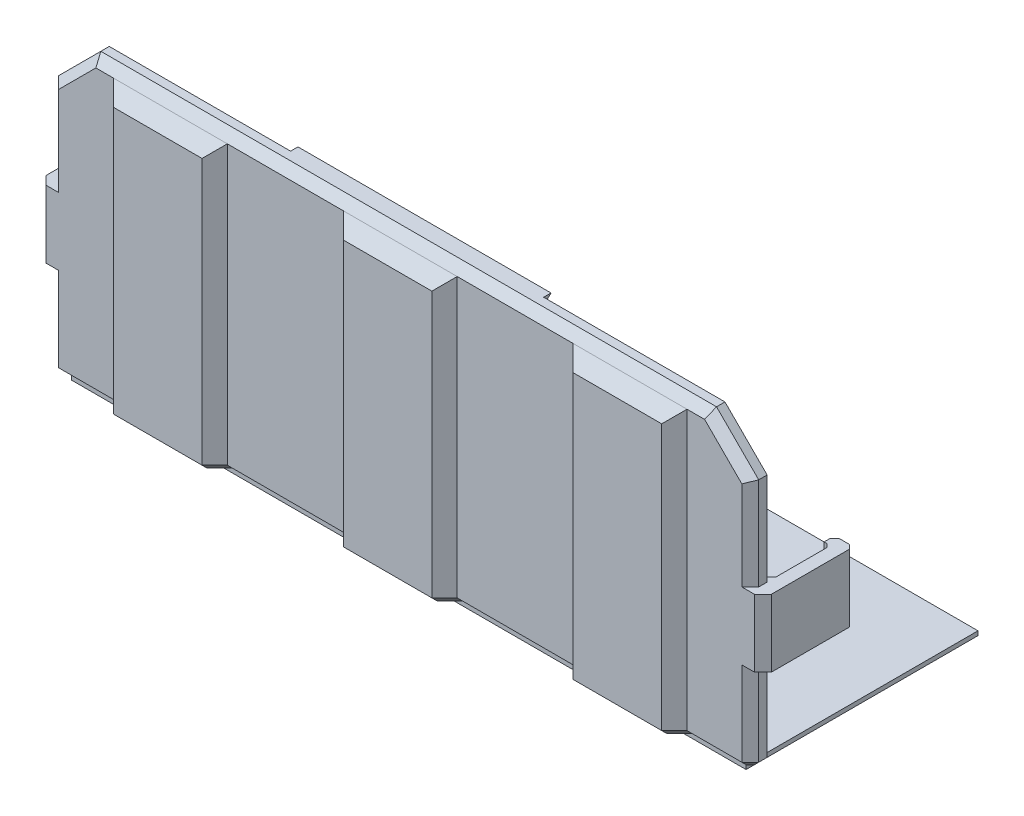
SolidWorks part; units mm, degrees
material "ABS PC"
ref_plane "Front Plane" through (0, 0, 0) normal (0, 0, 1) x (1, 0, 0)
ref_plane "Top Plane" through (0, 0, 0) normal (0, 1, 0) x (1, 0, 0)
ref_plane "Right Plane" through (0, 0, 0) normal (1, 0, 0) x (0, 0, -1)
sketch "Sketch1" plane through (0, 0, 0) normal (0, 0, 1) x (1, 0, 0)
  line L1 (83, -70) -> (-83, -70)
  line L2 (83, -70) -> (83, 0)
  line L3 (83, 0) -> (-83, 0)
  line L4 (-83, -70) -> (-83, 0)
  dimension "D1" = 166
  dimension "D2" = 70
extrude "Boss-Extrude1" add sketch "Sketch1" along normal blind 4
chamfer "Chamfer1" distance 10 angle 45 2 edges at (83, 0, 2) (-83, 0, 2)
chamfer "Chamfer2" distance 2 angle 45 5 edges at (83, -40, 4) (78, -5, 4) (-83, -40, 4) (-78, -5, 4) (0, 0, 4)
sketch "Sketch2" plane through (0, -70, 0) normal (0, -1, 0) x (-1, 0, 0)
  line L0 (68, -4) -> (65, -7)
  line L1 (81, -4) -> (-81, -4) construction
  line L2 (65, -7) -> (44, -7)
  line L3 (44, -7) -> (41, -4)
  line L4 (68, -4) -> (41, -4)
  line L5 (13.5, -4) -> (-13.5, -4)
  line L6 (-13.5, -4) -> (-10.5, -7)
  line L7 (-10.5, -7) -> (10.5, -7)
  line L8 (10.5, -7) -> (13.5, -4)
  line L9 (-41, -4) -> (-44, -7)
  line L10 (-44, -7) -> (-65, -7)
  line L11 (-65, -7) -> (-68, -4)
  line L12 (-68, -4) -> (-41, -4)
  line L13 (-47, 172) -> (-68, 172) construction
  line L14 (11, 172) -> (-11, 172) construction
  point P17 (0, 172)
  point P18 (0, -7)
  dimension "D1" = 45
  dimension "D2" = 3
extrude "Boss-Extrude2" add sketch "Sketch2" against normal up to vertex (68 mm away) up to point (72.1716, -2, 4)
chamfer "Chamfer3" distance 3 angle 45 3 edges at (54.5, -2, 7) (0, -2, 7) (-54.5, -2, 7)
sketch "Sketch3" plane through (0, -70, 0) normal (0, -1, 0) x (-1, 0, 0)
  line L0 (-73, -2) -> (-83, -2) construction
  line L1 (-80, -2) -> (80, -2)
  line L2 (-80, -2) -> (-80, 53)
  line L3 (-80, 53) -> (80, 53)
  line L4 (80, -2) -> (80, 53)
  line L5 (83, -2) -> (73, -2) construction
  dimension "D1" = 55
extrude "Boss-Extrude3" add sketch "Sketch3" along normal blind 3
chamfer "Chamfer4" distance 2 angle 45 3 edges at (0, -73, 2) (-80, -73, -25.5) (80, -73, -25.5)
ref_plane "Plane1" through (-70, 0, 0) normal (-1, 0, 0) x (0, 0, 1)
sketch "Sketch4" plane through (-70, 0, 0) normal (-1, 0, 0) x (0, 0, 1)
  line L0 (0, -70) -> (0, -65)
  line L1 (0, -10) -> (0, -70) construction
  line L2 (0, -65) -> (-5, -70)
  line L3 (0, -70) -> (-53, -70) construction
  line L4 (-5, -70) -> (0, -70)
  dimension "D1" = 5
extrude "Boss-Extrude4" add sketch "Sketch4" against normal offset from surface (140 mm away) 10 up to face at (80, -70.4, -20.4)
ref_plane "Plane2" through (0, -48, 0) normal (0, -1, 0) x (-1, 0, 0)
sketch "Sketch5" plane through (0, -48, 0) normal (0, -1, 0) x (-1, 0, 0)
  line L0 (-81, -4) -> (-83, -2)
  line L1 (-83, -2) -> (-83, 15)
  line L2 (-83, 15) -> (-81.5, 15)
  line L4 (-81.5, 15) -> (-81.5, 16.5)
  line L5 (-82.5, 17.5) -> (-85, 17.5)
  line L6 (-85, 17.5) -> (-86, 16.5)
  line L7 (-86, 16.5) -> (-86, -2)
  line L8 (-86, -2) -> (-84, -4)
  line L9 (-84, -4) -> (-81, -4)
  line L10 (-81.5, 16.5) -> (-82.5, 17.5)
  line L11 (0, 0) -> (0, 53) construction
  line L12 (78, 53) -> (-78, 53) construction
  line L13 (81.5, 16.5) -> (82.5, 17.5)
  line L14 (84, -4) -> (81, -4)
  line L15 (86, -2) -> (84, -4)
  line L16 (86, 16.5) -> (86, -2)
  line L17 (85, 17.5) -> (86, 16.5)
  line L18 (82.5, 17.5) -> (85, 17.5)
  line L19 (81.5, 15) -> (81.5, 16.5)
  line L20 (83, 15) -> (81.5, 15)
  line L21 (83, -2) -> (83, 15)
  line L22 (81, -4) -> (83, -2)
  dimension "D1" = 1.5
  dimension "D2" = 1.5
  dimension "D3" = 2.5
  dimension "D4" = 17
  dimension "D6" = 3
  dimension "D7" = 3
extrude "Boss-Extrude5" add sketch "Sketch5" against normal blind 16
chamfer "Chamfer5" distance 0.75 angle 45 2 edges at (-83, -40, -15) (83, -40, -15)
chamfer "Chamfer6" distance 2 angle 45 2 edges at (83, -40, 0) (-83, -40, 0)
chamfer "Chamfer7" distance 2 angle 45 17 edges at (-83, -70, 1) (-82, -70, 3) (83, -70, 1) (82, -70, 3) (66.5, -70, 5.5) (54.5, -70, 7) (42.5, -70, 5.5) (12, -70, 5.5) (0, -70, 7) (-12, -70, 5.5) (-54.5, -70, 7)
sketch "Sketch6" plane through (0, 0, 0) normal (1, 0, 0) x (0, 0, -1)
  line L0 (0, -1.75) -> (1.75, 0)
  line L1 (0, 0) -> (0, -10) construction
  line L2 (1.75, 0) -> (0, 0)
  line L3 (0, 0) -> (0, -1.75)
  dimension "D1" = 1.75
extrude "Boss-Extrude6" add sketch "Sketch6" along normal mid plane 60
